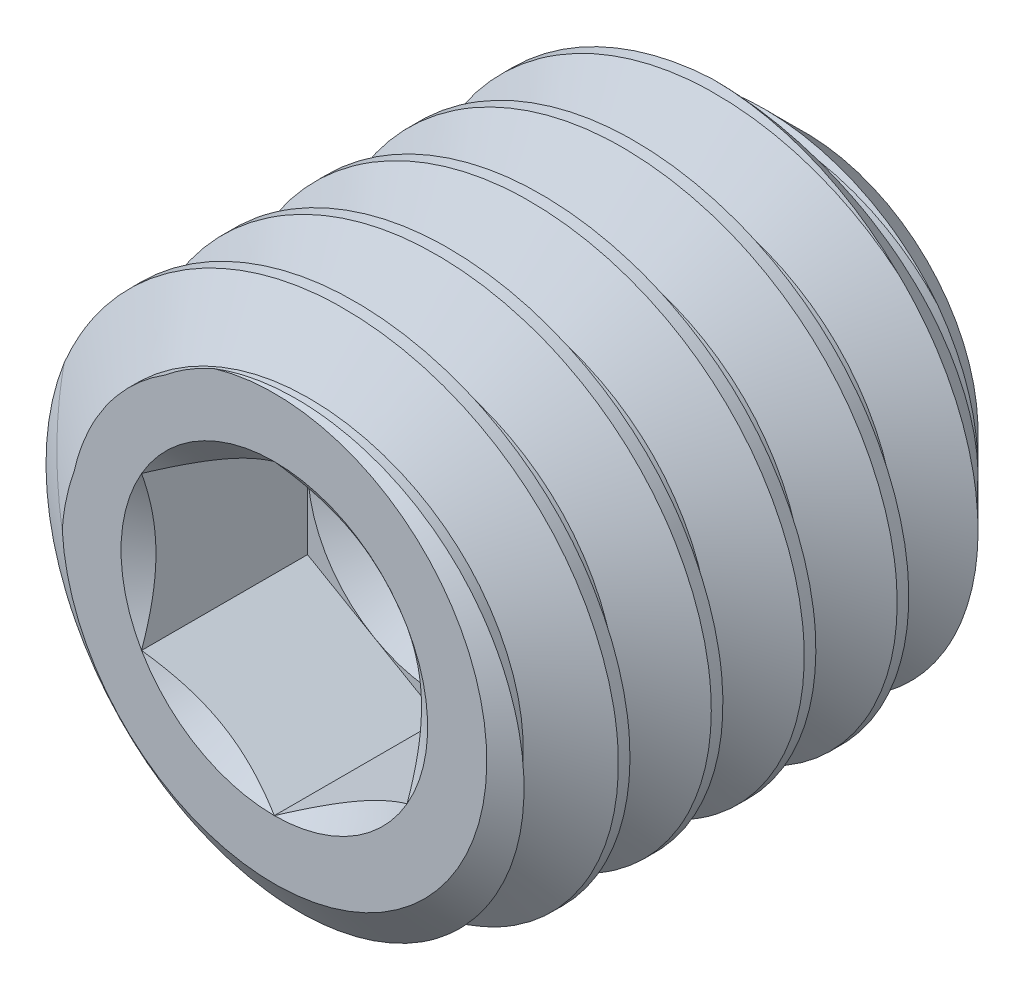
SolidWorks part; units mm, degrees
ref_plane "Front" through (0, 0, 0) normal (0, 0, 1) x (1, 0, 0)
ref_plane "Top" through (0, 0, 0) normal (0, 1, 0) x (1, 0, 0)
ref_plane "Right" through (0, 0, 0) normal (1, 0, 0) x (0, 0, -1)
sketch "Sketch22" plane through (0, 0, 0) normal (1, 0, 0) x (0, 0, -1)
  line L0 (-2, 0) -> (-2, 1.6)
  line L1 (-2, 1.6) -> (-1.7199, 2)
  line L2 (-1.7199, 2) -> (1.3, 2)
  line L3 (1.3, 2) -> (2, 1.3)
  line L4 (-0.21, 2) -> (-0.21, -2) construction
  line L5 (2, 0) -> (-2, 0)
  line L6 (-2, 1.6) -> (-2, -1.6) construction
  line L7 (2, 0) -> (2, 1.3)
  point P11 (-0.21, 0)
  dimension "Length" = 4
  dimension "D3" = 35
  dimension "D6" = 45
  dimension "Dia" = 4
  dimension "D1" = 3.2
  dimension "D2" = 0.7
revolve "Revolve1" add sketch "Sketch22" angle 360 about L5
ref_plane "Plane1" through (0, 0, -2) normal (0, 0, 1) x (1, 0, 0)
sketch "Sketch23" plane through (0, 0, 2) normal (0, 0, 1) x (1, 0, 0)
  line L1 (0, 1.1547) -> (-1, 0.5774)
  line L2 (-1, 0.5774) -> (-1, -0.5774)
  line L3 (-1, -0.5774) -> (0, -1.1547)
  line L4 (0, -1.1547) -> (1, -0.5774)
  line L5 (1, -0.5774) -> (1, 0.5774)
  line L6 (1, 0.5774) -> (0, 1.1547)
  circle A0 centre (0, 0) radius 1 construction
  dimension "Hex" = 2
extrude "Cut-Extrude10" cut sketch "Sketch23" against normal blind 1.25
sketch "Sketch24" plane through (0, 0, 2) normal (0, 0, 1) x (1, 0, 0)
  circle A0 centre (0, 0) radius 1.1547
extrude "Cut-Extrude11" cut sketch "Sketch24" against normal through all draft 55
sketch "Sketch26" plane through (0, 0, 0.75) normal (0, 0, 1) x (1, 0, 0)
  circle A0 centre (0, 0) radius 1 construction
  circle A1 centre (0, 0) radius 1
extrude "Cut-Extrude12" cut sketch "Sketch26" against normal through all draft 60
sketch "Sketch30" plane through (0, 0, 0) normal (1, 0, 0) x (0, 0, -1)
  line L0 (-1.7199, 2) -> (1.3, 2) construction
  line L1 (-2, 0) -> (-2, 1.6) construction
  line L2 (2, 0) -> (2, 1.3) construction
  point P0 (-2, 2)
  point P1 (2, 2)
  point P2 (2, -2)
  point P11 (0.25, -2)
  dimension "D1" = 1.75
sketch "Sketch27" plane through (0, 0, -2) normal (0, 0, 1) x (1, 0, 0)
  circle A0 centre (0, 0) radius 2 construction
  circle A1 centre (0, 0) radius 2
curve "Helix/Spiral1" pitch 0.7 height 4.7 radius 2 centre (0, 0, -2) axis (0, 0, 1) start towards (0, 1, 0)
sketch "Sketch28" plane through (0, 0, 0) normal (1, 0, 0) x (0, 0, -1)
  line L0 (2, 2) -> (2.6125, 2)
  line L1 (2.6125, 2) -> (2.35, 1.5453)
  line L2 (2.35, 1.5453) -> (2.2625, 1.5453)
  line L3 (2.2625, 1.5453) -> (2, 2)
  line L4 (2.1313, 1.7727) -> (2.4813, 1.7727) construction
  line L6 (-1.7199, 2) -> (1.3, 2) construction
  dimension "D1" = 0.0875
  dimension "D3" = 60
  dimension "D2" = 0.35
sweep "Cut-Sweep2" cut profiles "Sketch28" path "Helix/Spiral1"
ref_plane "Contact Plane 1" through (0, 0, 2) normal (0, 0, 1) x (1, 0, 0)
ref_plane "Contact Plane 2" through (0, 0, -2) normal (0, 0, -1) x (-1, 0, 0)
ref_axis "Center Axis 1" through (0, 0, -2) along (0, 0, 1)
equation "\"D1@Sketch28\" = \"D4@Helix/Spiral1\" * .125"
equation "\"D2@Sketch28\" = \"D4@Helix/Spiral1\" * .5"
equation "\"D3@Helix/Spiral1\" = \"Length@Sketch22\" + \"D4@Helix/Spiral1\""
equation "\"D1@Sketch30\" = \"D4@Helix/Spiral1\" * 2.5"
equation "\"hex Depth@Cut-Extrude10\" = \"Hex@Sketch23\" * .625"
equation "\"D1@Sketch22\" = \"Dia@Sketch22\" * .8"
equation "\"D2@Sketch22\" = \"D4@Helix/Spiral1\""
